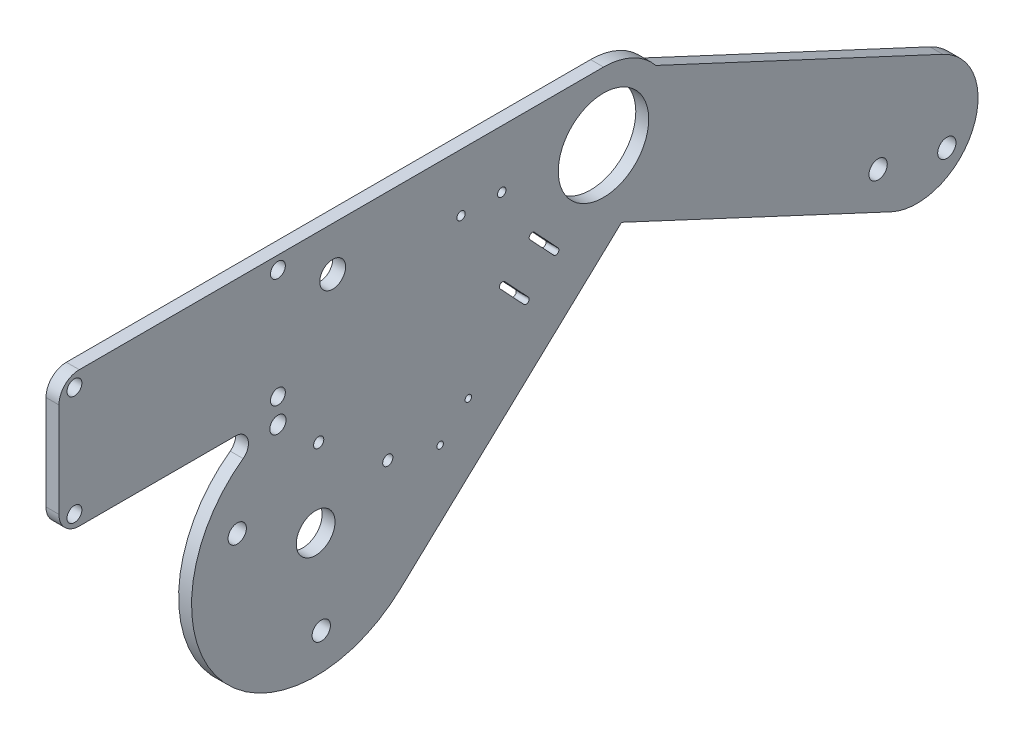
SolidWorks part; units mm, degrees
material "6061 Alloy"
ref_plane "Front Plane" through (0, 0, 0) normal (0, 0, 1) x (1, 0, 0)
ref_plane "Top Plane" through (0, 0, 0) normal (0, 1, 0) x (1, 0, 0)
ref_plane "Right Plane" through (0, 0, 0) normal (1, 0, 0) x (0, 0, -1)
sketch "Sketch1" plane through (0, 0, 0) normal (1, 0, 0) x (0, 0, -1)
  line L0 (-49.9001, -69.4268) -> (11.3662, -12.16)
  line L1 (-133.81, 16.645) -> (-76.19, 16.645)
  line L2 (-133.81, 16.645) -> (-133.81, -16.645)
  line L3 (-133.81, -16.645) -> (-76.19, -16.645)
  line L4 (-76.19, 16.645) -> (-76.19, -16.645)
  line L5 (-130, 13.475) -> (-80, 13.475)
  line L6 (-130, 13.475) -> (-130, -13.475)
  line L7 (-130, -13.475) -> (-80, -13.475)
  line L8 (-80, 13.475) -> (-80, -13.475)
  line L9 (-76.19, 16.645) -> (0, 16.645)
  line L10 (-83.2811, -19.3484) -> (-6.8511, 15.1697)
  line L11 (-130, -13.475) -> (-130, -19.435)
  line L12 (-80, -13.475) -> (-80, -19.435)
  line L13 (-76.19, -16.645) -> (0, -16.645)
  circle A0 centre (0, 0) radius 11.1125
  circle A1 centre (-70.7273, -47.145) radius 4.7625
  circle A2 centre (-70.7273, -47.145) radius 23.015 construction
  circle A3 centre (-70.7273, -47.145) radius 30.5
  circle A4 centre (0, 0) radius 16.645
  circle A5 centre (-130, -19.435) radius 2
  circle A6 centre (-80, -19.435) radius 2
  point P4 (-133.81, 0)
  point P12 (-130, 0)
  dimension "D6" = 22.225
  dimension "D7" = 9.525
  dimension "D8" = 46.03
  dimension "D9" = 61
  dimension "D11" = 0
  dimension "D14" = 4
  dimension "D1" = 33.29
  dimension "D2" = 80
  dimension "D3" = 26.95
  dimension "D4" = 50
  dimension "D5" = 3.81
  dimension "D10" = 85
  dimension "D12" = 3.81
  dimension "D13" = 5.96
extrude "Boss-Extrude1" add sketch "Sketch1" along normal mid plane 3.175 contours A6 A3 A1 | A4 L13 A3 L0 | A4 A0 | A4 L10 L4 L13 | A4 L9 L4 L10 | L8 L12 L3 L10 L4 L1 L2 L11 L6 L5 | L8 L5 L6 L7 | L12 L7 L11 L3 | A6 A3 L13 L3 L10 | L10 L3 L4 | A3 A6 | A3 A6 L10 L12 | L10 A6 A3 L12 | A6 L10 A3 region at (0, -30.4378, 28.398) region at (0, -63.5833, 95.3881) region at (0, -15.0453, -5.9367) region at (0, -18.8843, 82.226) region at (0, -7.4928, 34.7947) region at (0, -18.2558, 80.7031) region at (0, -19.6484, 79.9286) region at (0, -17.0177, 76.5839) region at (0, 5.7227, 51.9516) region at (0, -17.8085, 79.5096) region at (0, -16.4786, 76.5584) region at (0, -15.7889, 77.0165) region at (0, -15.06, 105) region at (0, 0, 105)
sketch "Sketch12" plane through (0, 0, 0) normal (1, 0, 0) x (0, 0, -1)
  line L0 (0, 0) -> (77.0362, -35.9226) construction
  line L1 (6.3393, 13.5946) -> (83.3754, -22.3279)
  line L2 (-6.3393, -13.5946) -> (70.6969, -49.5172)
  line L3 (-1000, 0) -> (49000, 0) construction
  line L5 (-4.9661, -14.2349) -> (77.7852, -34.0471) construction
  arc A0 (6.3393, 13.5946) -> (-6.3393, -13.5946) centre (0, 0) ccw
  arc A1 (70.6969, -49.5172) -> (83.3754, -22.3279) centre (77.0362, -35.9226) ccw
  circle A2 centre (0, 0) radius 11.1125 construction
  circle A3 centre (0, 0) radius 11.1125
  arc A5 (77.7852, -34.0471) -> (91.9205, -34.0633) centre (84.8868, -4.3854) ccw construction
  point P3 (38.5181, -17.9613)
  dimension "D1" = 85
  dimension "D2" = 30
  dimension "D3" = 25
extrude "Boss-Extrude2" add sketch "Sketch12" along normal mid plane 3.175 contours L2 A1 L1 A0 region at (0, -20.3901, -43.7267)
hole_wizard "#6 Clearance Hole1" positions "Sketch2" profile "Sketch3" hole size "#6" standard "ANSI Inch" end condition up to next
sketch "Sketch2" plane through (1.5875, 0, 0) normal (1, 0, 0) x (0, 0, -1)
  point P0 (-80, -13.475)
  point P3 (-80, 13.475)
  point P6 (-130, 13.475)
  point P9 (-130, -13.475)
sketch "Sketch3" plane through (1.5875, -13.475, 80) normal (0, 1, 0) x (0, 0, -1)
  line L0 (0, 0) -> (0, 3.175)
  line L1 (0, 3.175) -> (1.8288, 3.175)
  line L2 (1.8288, 3.175) -> (1.8288, 0)
  line L5 (1.8288, 0) -> (0, 0)
  line L11 (0, -6.35) -> (0, 107.95) construction
  dimension "Thru Hole Dia." = 3.6576
  dimension "Thru Hole Depth" = 3.175
hole_wizard "M3x0.5 Tapped Hole1" positions "Sketch4" profile "Sketch5" tap size "M3x0.5" standard "ANSI Metric" end condition up to next
sketch "Sketch4" plane through (1.5875, 0, 0) normal (1, 0, 0) x (0, 0, -1)
  line L7 (-70.7273, -47.145) -> (-41.414, -6.6391) construction
  line L9 (-69.9837, -28.2416) -> (-53.0036, -40.5297) construction
  point P121 (-61.4936, -34.3856)
  point P124 (-69.9837, -28.2416)
  point P127 (-53.0036, -40.5297)
  dimension "D1" = 20.96
  dimension "D2" = 15.75
  dimension "D3" = 135
  dimension "D4" = 50
sketch "Sketch5" plane through (1.5875, -40.5297, 53.0036) normal (0, 1, 0) x (0, 0, -1)
  line L0 (0, 0) -> (0, 3.175)
  line L1 (0, 3.175) -> (1.25, 3.175)
  line L2 (1.25, 3.175) -> (1.25, 0)
  line L5 (1.25, 0) -> (0, 0)
  line L11 (0, -6.35) -> (0, 107.95) construction
  dimension "Thru Tap Drill Dia." = 2.5
  dimension "Thru Tap Drill Depth" = 3.175
hole_wizard "M4 Clearance Hole1" positions "Sketch6" profile "Sketch7" hole size "M4" standard "ANSI Metric" end condition up to next
sketch "Sketch6" plane through (1.5875, 0, 0) normal (1, 0, 0) x (0, 0, -1)
  line L0 (-70.7273, -47.145) -> (-69.3449, -68.6005) construction
  line L1 (-70.7273, -47.145) -> (-89.9995, -37.6144) construction
  line L3 (-70.7273, -47.145) -> (0, 0) construction
  line L7 (77.0362, -35.9226) -> (84.3628, -42.7285) construction
  line L9 (77.0362, -35.9226) -> (67.4787, -38.8646) construction
  line L10 (77.0362, -35.9226) -> (0, 0) construction
  point P2 (-69.3449, -68.6005)
  point P16 (-89.9995, -37.6144)
  point P37 (67.4787, -38.8646)
  point P40 (84.3628, -42.7285)
  dimension "D1" = 21.5
  dimension "D2" = 120
  dimension "D3" = 120
  dimension "D4" = 120
  dimension "D5" = 10
  dimension "D6" = 17.89
  dimension "D7" = 0
sketch "Sketch7" plane through (1.5875, -42.7285, -84.3628) normal (0, 1, 0) x (0, 0, -1)
  line L0 (0, 0) -> (0, 3.175)
  line L1 (0, 3.175) -> (2.25, 3.175)
  line L2 (2.25, 3.175) -> (2.25, 0)
  line L5 (2.25, 0) -> (0, 0)
  line L11 (0, -6.35) -> (0, 107.95) construction
  dimension "Thru Hole Dia." = 4.5
  dimension "Thru Hole Depth" = 3.175
hole_wizard "M2x0.4 Tapped Hole1" positions "Sketch8" profile "Sketch9" tap size "M2x0.4" standard "ANSI Metric" end condition up to next
sketch "Sketch8" plane through (1.5875, 0, 0) normal (1, 0, 0) x (0, 0, -1)
  line L0 (-49.9001, -69.4268) -> (4.4493, -18.6254) construction
  line L2 (0, 0) -> (34142.961, -36527.4995) construction
  point P0 (-33.212, -37.2653)
  point P2 (-40.1523, -43.7524)
  dimension "D1" = 12.1
  dimension "D2" = 9.5
  dimension "D3" = 12.1
  dimension "D4" = 49.71
sketch "Sketch9" plane through (1.5875, -37.2653, 33.212) normal (0, 1, 0) x (0, 0, -1)
  line L0 (0, 0) -> (0, 3.175)
  line L1 (0, 3.175) -> (0.8, 3.175)
  line L2 (0.8, 3.175) -> (0.8, 0)
  line L5 (0.8, 0) -> (0, 0)
  line L11 (0, -6.35) -> (0, 107.95) construction
  dimension "Thru Tap Drill Dia." = 1.6
  dimension "Thru Tap Drill Depth" = 3.175
cosmetic thread "Hole Thread1" parameters "D2"=2
cosmetic thread "Hole Thread2" parameters "D2"=2
fillet "Fillet1" radius 5 2 edges at (0, -16.645, 133.81) (0, 16.645, 133.81)
fillet "Fillet2" radius 3.175 1 edges at (0, -16.645, 77.2953)
extrude "Cut-Extrude1" cut sketch "Sketch1<3>" against normal through all both and the other way through all contours A3 A6 | A3 A6 L10 L12 | L12 A6 L10 | L10 A6 A3 L12 | L10 A6 L12 region at (0, -17.9759, 80.8435) region at (0, -18.2558, 80.7031) region at (0, -19.6484, 79.9286) region at (0, -17.6074, 79.7609) region at (0, -17.8085, 79.5096)
sketch "Sketch1<3>" plane through (0, 0, 0) normal (1, 0, 0) x (0, 0, -1) same geometry as "Sketch1"
hole_wizard "1/4 (0.2500) Dowel Hole1" positions "Sketch10" profile "Sketch11" hole size "1/4" standard "ANSI Inch" end condition up to next
sketch "Sketch10" plane through (1.5875, 0, 0) normal (1, 0, 0) x (0, 0, -1)
  line L0 (-66.5458, 5.822) -> (0, 0) construction
  line L2 (-1000, 0) -> (49000, 0) construction
  point P0 (-66.5458, 5.822)
  dimension "D1" = 66.8
  dimension "D2" = 5
sketch "Sketch11" plane through (1.5875, 5.822, 66.5458) normal (0, 1, 0) x (0, 0, -1)
  line L0 (0, 0) -> (0, 3.175)
  line L1 (0, 3.175) -> (3.175, 3.175)
  line L2 (3.175, 3.175) -> (3.175, 0)
  line L5 (3.175, 0) -> (0, 0)
  line L11 (0, -6.35) -> (0, 107.95) construction
  dimension "Thru Hole Dia." = 6.35
  dimension "Thru Hole Depth" = 3.175
sketch "Sketch13" plane through (1.5875, 0, 0) normal (1, 0, 0) x (0, 0, -1)
  line L0 (-4.9661, -14.2349) -> (77.7852, -34.0471) construction
  line L1 (-4.9661, -14.2349) -> (77.7852, -34.0471)
  line L2 (-6.3393, -13.5946) -> (70.6969, -49.5172) construction
  line L3 (-4.9661, -14.2349) -> (70.6969, -49.5172)
  arc A0 (77.7852, -34.0471) -> (91.9205, -34.0633) centre (84.8868, -4.3854) ccw construction
  arc A1 (77.7852, -34.0471) -> (91.9205, -34.0633) centre (84.8868, -4.3854) ccw
  arc A2 (70.6969, -49.5172) -> (83.3754, -22.3279) centre (77.0362, -35.9226) ccw construction
  arc A3 (70.6969, -49.5172) -> (91.9205, -34.0633) centre (77.0362, -35.9226) ccw
extrude "Boss-Extrude3" [suppressed] add sketch "Sketch13" along normal blind 10
hole_wizard "Ø1.5mm Dowel Slot1" positions "Sketch14" profile "Sketch15" size "Ø1.5" standard "ANSI Metric" slot yes end condition up to next
sketch "Sketch14" plane through (1.5875, 0, 0) normal (1, 0, 0) x (0, 0, -1)
  line L0 (-18.5022, -24.1385) -> (-25.3308, -16.833) construction
  line L3 (-21.9165, -20.4858) -> (-14.611, -13.6572) construction
  line L6 (-49.9001, -69.4268) -> (4.4493, -18.6254) construction
  point P0 (-21.9165, -20.4858)
  point P4 (-14.611, -13.6572)
  dimension "D1" = 10
  dimension "D2" = 10
  dimension "D3" = 20
sketch "Sketch15" plane through (1.5875, -20.4858, 21.9165) normal (0, 1, 0) x (0, 0, -1)
  line L0 (0, 0) -> (0, 3.175)
  line L1 (0, 3.175) -> (0.75, 3.175)
  line L2 (0.75, 3.175) -> (0.75, 0)
  line L5 (0.75, 0) -> (0, 0)
  line L11 (0, -6.35) -> (0, 107.95) construction
  dimension "Thru Hole Dia." = 1.5
  dimension "Thru Hole Depth" = 3.175
hole_wizard "M2.5x0.45 Tapped Hole1" positions "Sketch16" profile "Sketch17" tap size "M2.5x0.45" standard "ANSI Metric" end condition up to next
sketch "Sketch16" plane through (1.5875, 0, 0) normal (1, 0, 0) x (0, 0, -1)
  line L0 (-128.81, 16.645) -> (0, 16.645) construction
  point P0 (-35, 2.5)
  point P2 (-25, 2.5)
  point P5 (0, 0)
  dimension "D1" = 10
  dimension "D2" = 14.145
  dimension "D3" = 25
sketch "Sketch17" plane through (1.5875, 2.5, 35) normal (0, 1, 0) x (0, 0, -1)
  line L0 (0, 0) -> (0, 3.175)
  line L1 (0, 3.175) -> (1.025, 3.175)
  line L2 (1.025, 3.175) -> (1.025, 0)
  line L5 (1.025, 0) -> (0, 0)
  line L11 (0, -6.35) -> (0, 107.95) construction
  dimension "Thru Tap Drill Dia." = 2.05
  dimension "Thru Tap Drill Depth" = 3.175
cosmetic thread "Hole Thread3" parameters "D2"=2.5
cosmetic thread "Hole Thread4" parameters "D2"=2.5
